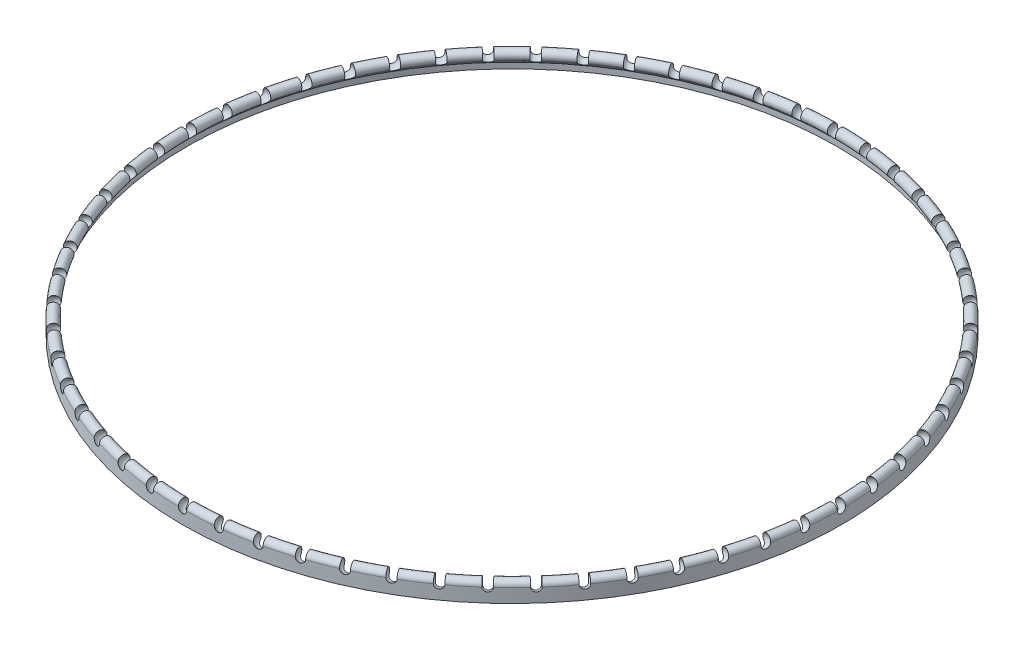
SolidWorks part; units mm, degrees
ref_plane "Front Plane" through (0, 0, 0) normal (0, 0, 1) x (1, 0, 0)
ref_plane "Top Plane" through (0, 0, 0) normal (0, 1, 0) x (1, 0, 0)
ref_plane "Right Plane" through (0, 0, 0) normal (1, 0, 0) x (0, 0, -1)
sketch "Sketch4" plane through (0, 0, 0) normal (0, 1, 0) x (1, 0, 0)
  circle A0 centre (0, 0) radius 125 construction
ref_axis "Axis2" through (0, 0, 0) along (0, 1, 0)
sketch "Sketch3" plane through (0, 0, 0) normal (0, 0, 1) x (1, 0, 0)
  line L0 (0, 0) -> (0, 50000) construction
  line L1 (-125, 0) -> (125, 0) construction
  line L2 (125, -6) -> (-49875, -6) construction
  line L4 (125, 0) -> (125, -6) construction
  line L5 (-125, 0) -> (-125, -6) construction
  line L6 (-124, -8.95) -> (-116.1509, -8.95)
  line L7 (-117.8491, -13.05) -> (-113, -13.05)
  line L8 (-117.8491, -13.05) -> (-119.8991, -11)
  line L9 (-116.1509, -8.95) -> (-114.1009, -11)
  line L10 (-119.8991, -11) -> (-114.1009, -11) construction
  line L11 (-119.8991, -11) -> (-124, -11)
  line L12 (-125, -12) -> (-125, -29)
  line L13 (-125, -29) -> (-114.05, -29)
  line L14 (-125, -7.95) -> (-125, 0)
  line L15 (-125, 0) -> (125, 0)
  line L16 (-114.1009, -11) -> (-110.95, -11)
  line L17 (-111, -28) -> (-101, -28)
  line L20 (-112, -14.05) -> (-112, -18.1009)
  line L21 (-112, -18.1009) -> (-114.05, -20.1509)
  line L22 (-109.95, -21.8491) -> (-112, -23.8991)
  line L23 (-114.05, -20.1509) -> (-114.05, -29)
  line L24 (-112, -18.1009) -> (-112, -33.5423) construction
  line L25 (-112, -23.8991) -> (-112, -27)
  line L26 (-101, 0) -> (-125, 0)
  line L27 (-109.95, -12) -> (-109.95, -16.9246)
  line L29 (-101, -16.9246) -> (-101, 0)
  line L30 (-109.95, -16.9246) -> (-109.95, -21.8491)
  line L31 (-101, -16.9246) -> (-101, -28)
  line L32 (-101, -16.9246) -> (-109.95, -16.9246)
  line L33 (-121.7749, -11) -> (-121.7749, -10.7) construction
  line L34 (-121.7749, -8.95) -> (-121.7749, -9.25)
  line L35 (-121.7749, -9.25) -> (-117, -9.25)
  line L36 (-121.7749, -10.7) -> (-119.7749, -10.7)
  line L37 (-119.7749, -10.7) -> (-118.2374, -12.2374)
  line L38 (-117, -11) -> (-118.2374, -12.2374) construction
  line L39 (-121.7749, -10.7) -> (-121.7749, -9.25)
  line L40 (-112, -25.7749) -> (-112.3, -25.7749) construction
  line L41 (-114.05, -25.7749) -> (-113.75, -25.7749) construction
  line L42 (-113.75, -25.7749) -> (-113.75, -21)
  line L43 (-112.3, -25.7749) -> (-112.3, -23.7749)
  line L44 (-112.3, -23.7749) -> (-110.7626, -22.2374)
  line L45 (-112, -21) -> (-110.7626, -22.2374) construction
  line L46 (-112.3, -25.7749) -> (-113.75, -25.7749)
  line L47 (-112, -18.75) -> (-112, -23.25)
  circle A0 centre (-117, -11) radius 2.05 construction
  circle A1 centre (-112, -21) radius 2.05 construction
  arc A2 (-109.95, -12) -> (-110.95, -11) centre (-110.95, -12) ccw
  arc A3 (-112, -14.05) -> (-113, -13.05) centre (-113, -14.05) ccw
  arc A4 (-112, -27) -> (-111, -28) centre (-111, -27) ccw
  arc A5 (-124, -8.95) -> (-125, -7.95) centre (-124, -7.95) cw
  arc A6 (-124, -11) -> (-125, -12) centre (-124, -12) ccw
  arc A7 (-117, -9.25) -> (-118.2374, -12.2374) centre (-117, -11) cw
  arc A8 (-110.7626, -22.2374) -> (-113.75, -21) centre (-112, -21) ccw
  circle A9 centre (-112, -21) radius 2.25
  point P6 (0, 0)
  point P23 (-117, -11)
  point P31 (-117, -11)
  point P38 (-112, -28)
  point P48 (-125, -11)
  dimension "D3" = 4.1
  dimension "D4" = 45
  dimension "D8" = 4.1
  dimension "D9" = 1
  dimension "D13" = 1
  dimension "D17" = 1
  dimension "D18" = 1
  dimension "D19" = 2
  dimension "D24" = 2
  dimension "D1" = 250
  dimension "D2" = 6
  dimension "D5" = 45
  dimension "D6" = 8
  dimension "D7" = 5
  dimension "D10" = 0.3
  dimension "D11" = 15
  dimension "D12" = 13
  dimension "D14" = 0.3
  dimension "D15" = 18
  dimension "D16" = 0.3
  dimension "D20" = 0.3
  dimension "D21" = 0.3
  dimension "D22" = 0.3
  dimension "D23" = 45
revolve "Revolve5" add sketch "Sketch3" angle 360 about axis through (0, 0, 0) along (0, 1, 0) region at (-111.2804, -21.1116, 0) region at (-112.7867, -21.2967, 0) region at (-113.0275, -24.3195, 0)
revolve "Cut-Revolve1" cut sketch "Sketch3<9>" angle 360 about L24 region at (-109.8335, -20.5328, 0) region at (-109.9993, -20.9609, 0) region at (-111.2804, -21.1116, 0)
sketch "Sketch3<9>" plane through (0, 0, 0) normal (0, 0, 1) x (1, 0, 0) same geometry as "Sketch3"
pattern_circular "CirPattern1" count 60 every 6 about axis through (0, 0, 0) along (0, 1, 0) of "Cut-Revolve1"
